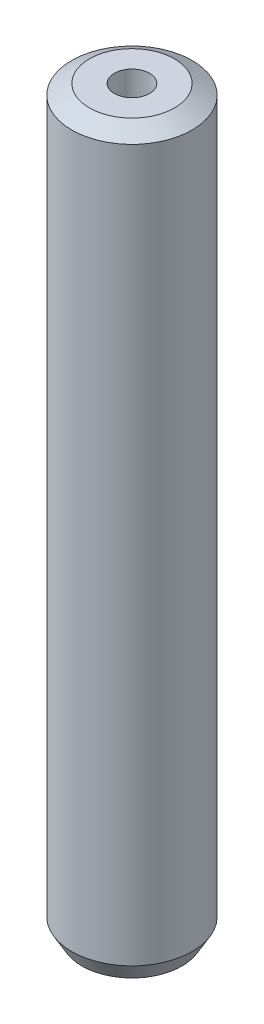
SolidWorks part; units mm, degrees
ref_plane "Front Plane" through (0, 0, 0) normal (0, 0, 1) x (1, 0, 0)
ref_plane "Top Plane" through (0, 0, 0) normal (0, 1, 0) x (1, 0, 0)
ref_plane "Right Plane" through (0, 0, 0) normal (1, 0, 0) x (0, 0, -1)
sketch "Sketch1" plane through (0, 0, 0) normal (0, 1, 0) x (1, 0, 0)
  circle A0 centre (0, 0) radius 27.5
  dimension "SHAFT_OD" = 55
extrude "Boss-Extrude1" add sketch "Sketch1" along normal blind 337.4218
sketch "Sketch2" plane through (0, 0, 0) normal (0, 1, 0) x (1, 0, 0)
  circle A0 centre (0, 0) radius 8.028
  dimension "BORE_D" = 16.056
extrude "Cut-Extrude1" cut sketch "Sketch2" along normal through all
chamfer "Chamfer1" distance 4.6689 angle 60 2 edges at (0, 337.4218, 27.5) (0, 0, 27.5) first distance on face at (0, 337.4218, 27.5) first distance on face at (0, 0, 8.028)
